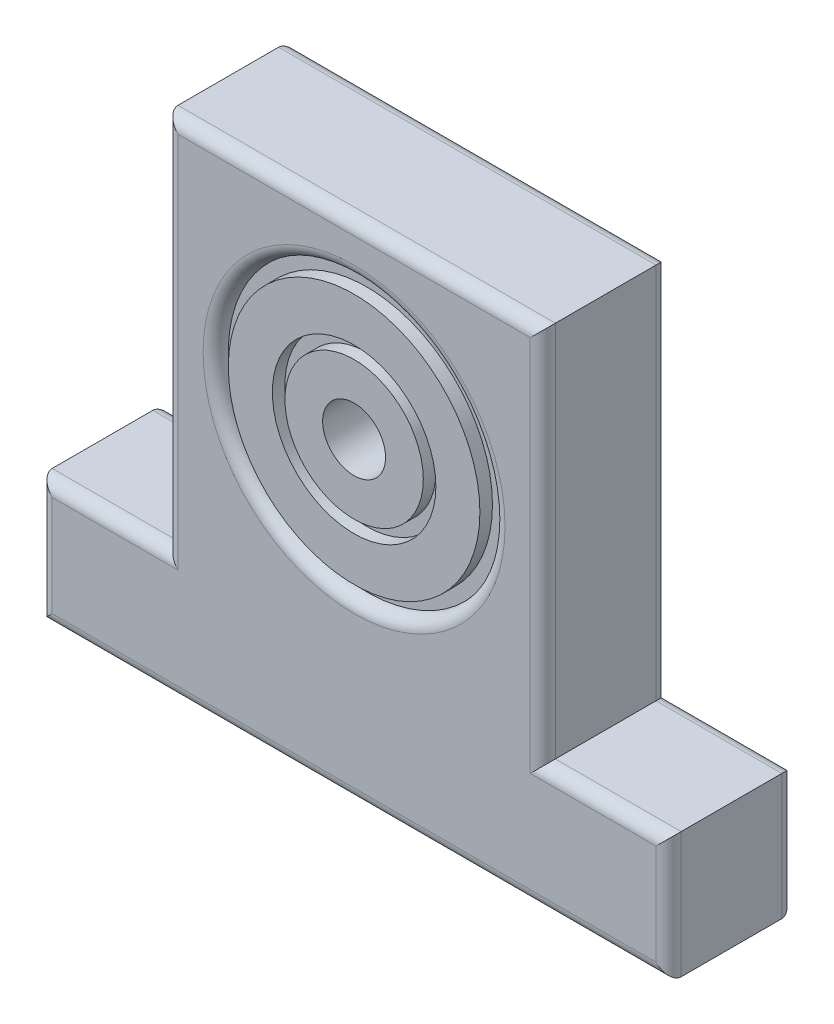
SolidWorks part; units mm, degrees
ref_plane "Front Plane" through (0, 0, 0) normal (0, 0, 1) x (1, 0, 0)
ref_plane "Top Plane" through (0, 0, 0) normal (0, 1, 0) x (1, 0, 0)
ref_plane "Right Plane" through (0, 0, 0) normal (1, 0, 0) x (0, 0, -1)
sketch "Sketch1" plane through (0, 0, 0) normal (0, 0, 1) x (1, 0, 0)
  line L0 (0, 0) -> (50, 0)
  line L1 (50, 0) -> (50, 10)
  line L2 (50, 10) -> (40, 10)
  line L3 (40, 10) -> (40, 40)
  line L4 (40, 40) -> (10, 40)
  line L5 (10, 40) -> (10, 10)
  line L6 (10, 10) -> (0, 10)
  line L7 (0, 10) -> (0, 0)
  line L8 (10, 40) -> (40, 10) construction
  line L9 (40, 40) -> (10, 10) construction
  circle A0 centre (25, 25) radius 2.5
  circle A1 centre (25, 25) radius 11
  dimension "D5" = 5
  dimension "D6" = 22
  dimension "D1" = 30
  dimension "D2" = 10
  dimension "D3" = 10
  dimension "D4" = 30
extrude "Boss-Extrude1" add sketch "Sketch1" along normal blind 10 contours L0 L1 L2 L3 L4 L5 L6 L7 | A0
sketch "Sketch2" plane through (0, 0, 10) normal (0, 0, 1) x (1, 0, 0)
  circle A0 centre (25, 25) radius 2.5 construction
  circle A1 centre (25, 25) radius 2.5
  circle A2 centre (25, 25) radius 10
  circle A3 centre (25, 25) radius 6.5
  circle A4 centre (25, 25) radius 5.5
  circle A5 centre (25, 25) radius 11
  point P8 (0, 0)
  dimension "D1" = 22
  dimension "D2" = 1
  dimension "D3" = 11
  dimension "D4" = 1
extrude "Cut-Extrude1" cut sketch "Sketch2" against normal blind 1 contours A3 A4 | A5 A2 region at (18.6838, 25, 10) region at (14.3111, 25, 10)
ref_plane "Plane1" through (0, 0, 5) normal (0, 0, 1) x (1, 0, 0)
mirror "Mirror1" about plane through (0, 0, 5) normal (0, 0, 1) of "Cut-Extrude1"
fillet "Fillet1" radius 1 18 edges at (25, 0, 0) (50, 5, 0) (45, 10, 0) (40, 25, 0) (25, 40, 0) (10, 25, 0) (5, 10, 0) (0, 5, 0) (36, 25, 0) (5, 10, 10) (10, 25, 10) (25, 40, 10) (40, 25, 10) (45, 10, 10) (50, 5, 10) (25, 0, 10) (0, 5, 10) (36, 25, 10)
